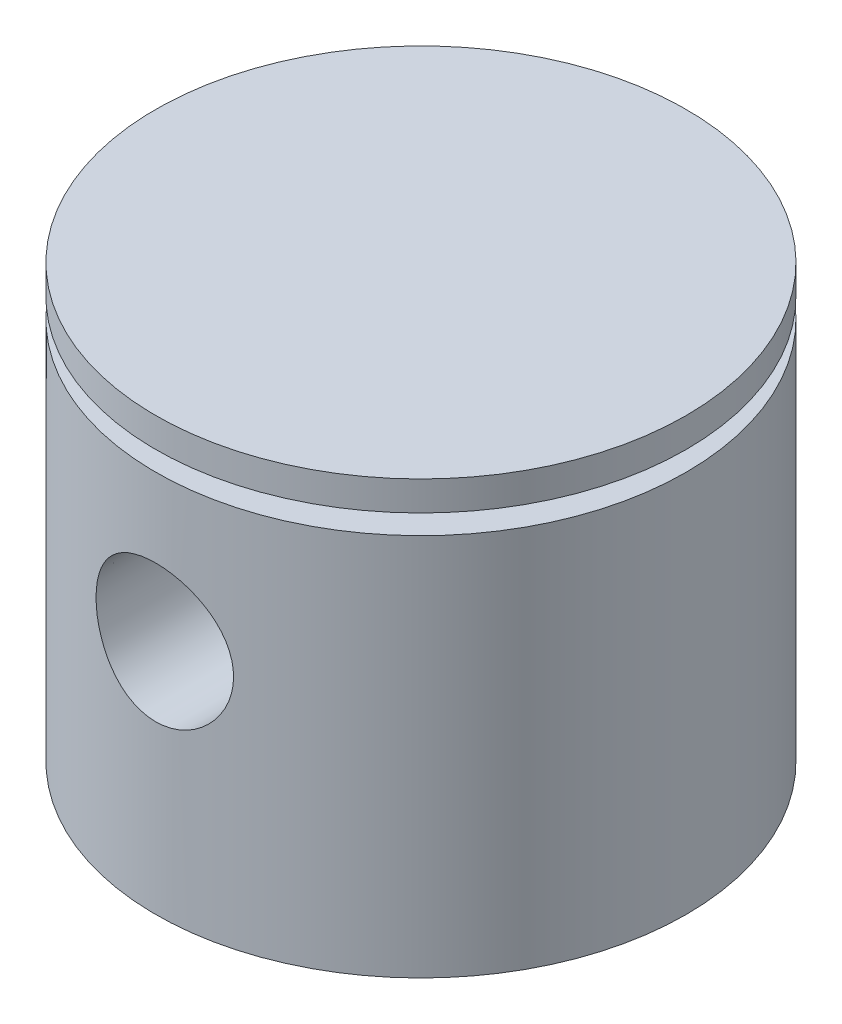
SolidWorks part; units mm, degrees
ref_plane "Plan de face" through (0, 0, 0) normal (0, 0, 1) x (1, 0, 0)
ref_plane "Plan de dessus" through (0, 0, 0) normal (0, 1, 0) x (1, 0, 0)
ref_plane "Plan de droite" through (0, 0, 0) normal (1, 0, 0) x (0, 0, -1)
sketch "Esquisse1" plane through (0, 0, 0) normal (0, 0, 1) x (1, 0, 0)
  line L0 (0, 0) -> (5.8224, 0)
  line L1 (5.8224, 0) -> (5.8224, 60)
  line L2 (5.8224, 60) -> (55.8224, 60)
  line L3 (55.8224, 60) -> (55.8224, 190)
  line L4 (55.8224, 190) -> (125.8224, 190)
  line L5 (125.8224, 190) -> (125.8224, 220)
  line L6 (125.8224, 220) -> (-9.1776, 220)
  line L7 (-9.1776, 220) -> (-9.1776, 205)
  line L8 (-9.1776, 205) -> (10.8224, 205)
  line L9 (10.8224, 205) -> (10.8224, 195)
  line L10 (10.8224, 195) -> (-9.1776, 195)
  line L11 (-9.1776, 195) -> (-9.1776, 0)
  line L12 (-9.1776, 0) -> (0, 0)
  dimension "D1" = 135
  dimension "D2" = 30
  dimension "D3" = 70
  dimension "D4" = 130
  dimension "D5" = 10
  dimension "D6" = 20
  dimension "D7" = 20
  dimension "D8" = 220
  dimension "D9" = 50
  dimension "D10" = 15
  dimension "D11" = 9.1776
  dimension "D12" = 5.8224
revolve "Révolution1" add sketch "Esquisse1" angle 360 about L5
sketch "Esquisse2" plane through (0, 0, 0) normal (0, 0, 1) x (1, 0, 0)
  line L0 (260.8224, 220) -> (-9.1776, 220) construction
  line L1 (260.8224, 0) -> (260.8224, 195) construction
  circle A0 centre (125.8224, 120) radius 35
  dimension "D1" = 70
  dimension "D2" = 100
  dimension "D3" = 135
extrude "Enlèv. mat.-Extru.1" cut sketch "Esquisse2" against normal through all from surface contours A0
